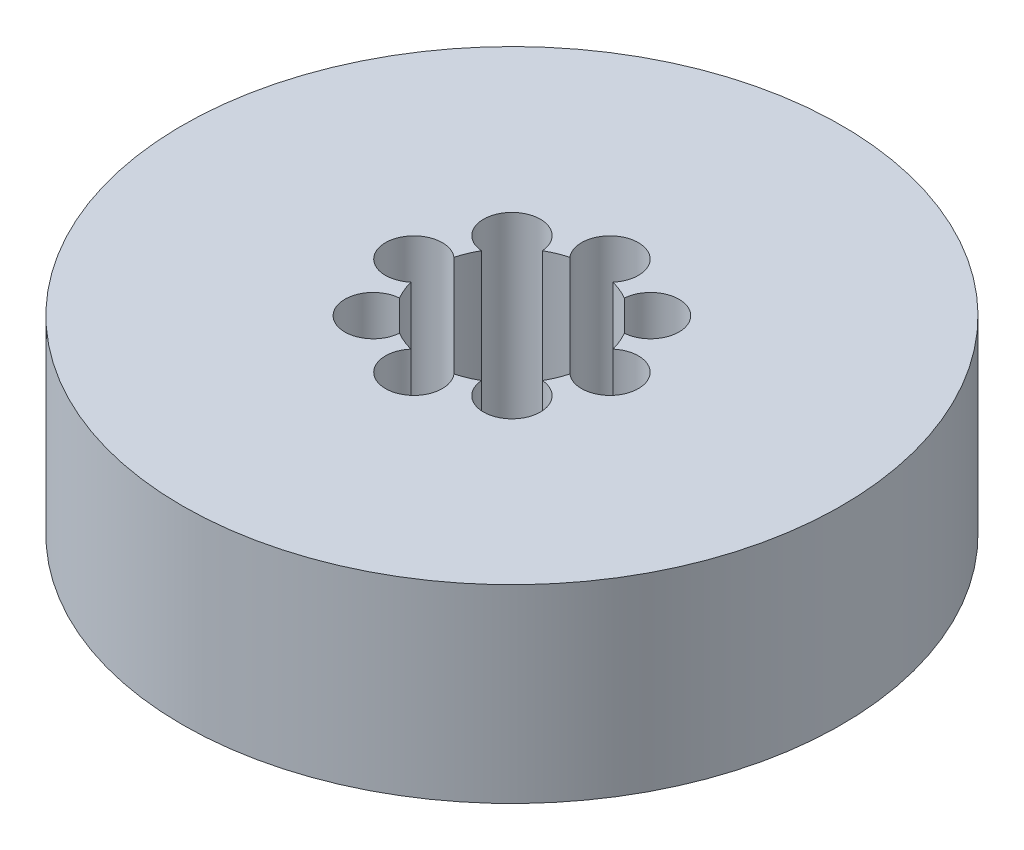
SolidWorks part; units mm, degrees
ref_plane "Front Plane" through (0, 0, 0) normal (0, 0, 1) x (1, 0, 0)
ref_plane "Top Plane" through (0, 0, 0) normal (0, 1, 0) x (1, 0, 0)
ref_plane "Right Plane" through (0, 0, 0) normal (1, 0, 0) x (0, 0, -1)
sketch "Sketch1" plane through (0, 0, 0) normal (0, 1, 0) x (1, 0, 0)
  circle A0 centre (0, 0) radius 40
  dimension "FLANGE_OD" = 80
extrude "Boss-Extrude1" add sketch "Sketch1" along normal blind 23
sketch "Sketch2" plane through (0, 0, 0) normal (0, 1, 0) x (1, 0, 0)
  circle A0 centre (0, 0) radius 10
  dimension "BORE_D" = 20
extrude "Cut-Extrude1" cut sketch "Sketch2" along normal through all
sketch "Sketch3" plane through (0, 23, 0) normal (0, 1, 0) x (1, 0, 0)
  circle A0 centre (0, 0) radius 11.8988 construction
  circle A1 centre (-11.8988, 0) radius 3.4505
  dimension "BOLT_D" = 6.901
  dimension "BOLT_PCD" = 23.7975
extrude "Cut-Extrude2" cut sketch "Sketch3" against normal blind 22.2758
pattern_circular "CirPattern1" count 8 over 360 about axis through (0, 0, 0) along (0, 1, 0) of "Cut-Extrude2"
